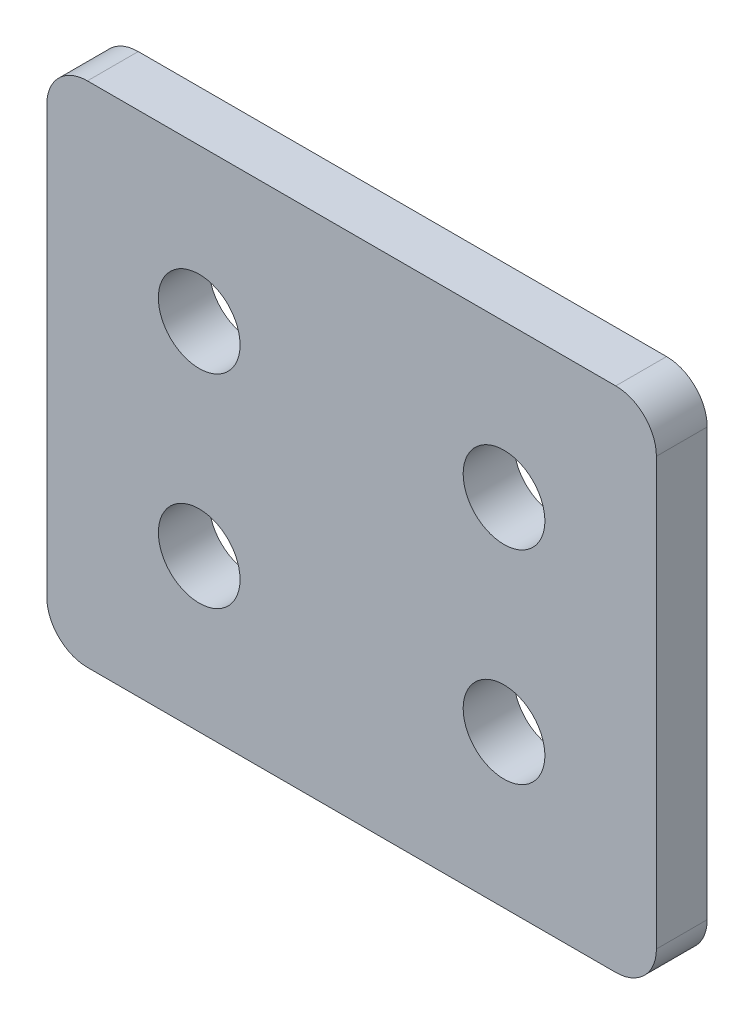
SolidWorks part; units mm, degrees
material "6061-T6 (SS)"
ref_plane "Front Plane" through (0, 0, 0) normal (0, 0, 1) x (1, 0, 0)
ref_plane "Top Plane" through (0, 0, 0) normal (0, 1, 0) x (1, 0, 0)
ref_plane "Right Plane" through (0, 0, 0) normal (1, 0, 0) x (0, 0, -1)
sketch "Sketch1" plane through (0, 0, 0) normal (0, 0, 1) x (1, 0, 0)
  line L0 (-9.525, -6.35) -> (-9.525, 6.35) construction
  line L5 (-19.05, -15.875) -> (19.05, -15.875)
  line L6 (-19.05, -15.875) -> (-19.05, 15.875)
  line L11 (-19.05, 15.875) -> (19.05, 15.875)
  line L15 (19.05, -15.875) -> (19.05, 15.875)
  line L16 (-19.05, -15.875) -> (19.05, 15.875) construction
  line L17 (-19.05, 15.875) -> (19.05, -15.875) construction
  line L18 (0, 15.875) -> (0, -15.875) construction
  circle A13 centre (-9.525, -6.35) radius 2.5527
  circle A14 centre (-9.525, 6.35) radius 2.5527
  circle A17 centre (9.525, -6.35) radius 2.5527
  circle A18 centre (9.525, 6.35) radius 2.5527
  point P0 (0, 0)
  point P11 (9.525, 3.1792)
  point P12 (0, 0)
  point P13 (-9.525, 0)
  dimension "D2" = 12.7
  dimension "D4" = 19.05
  dimension "D5" = 5.1054
  dimension "D7" = 31.75
  dimension "D1" = 2
  dimension "D6" = 38.1
extrude "Boss-Extrude1" add sketch "Sketch1" along normal blind 3.175
fillet "Fillet1" radius 2.54 4 edges at (-19.05, 15.875, 1.5875) (-19.05, -15.875, 1.5875) (19.05, -15.875, 1.5875) (19.05, 15.875, 1.5875)
